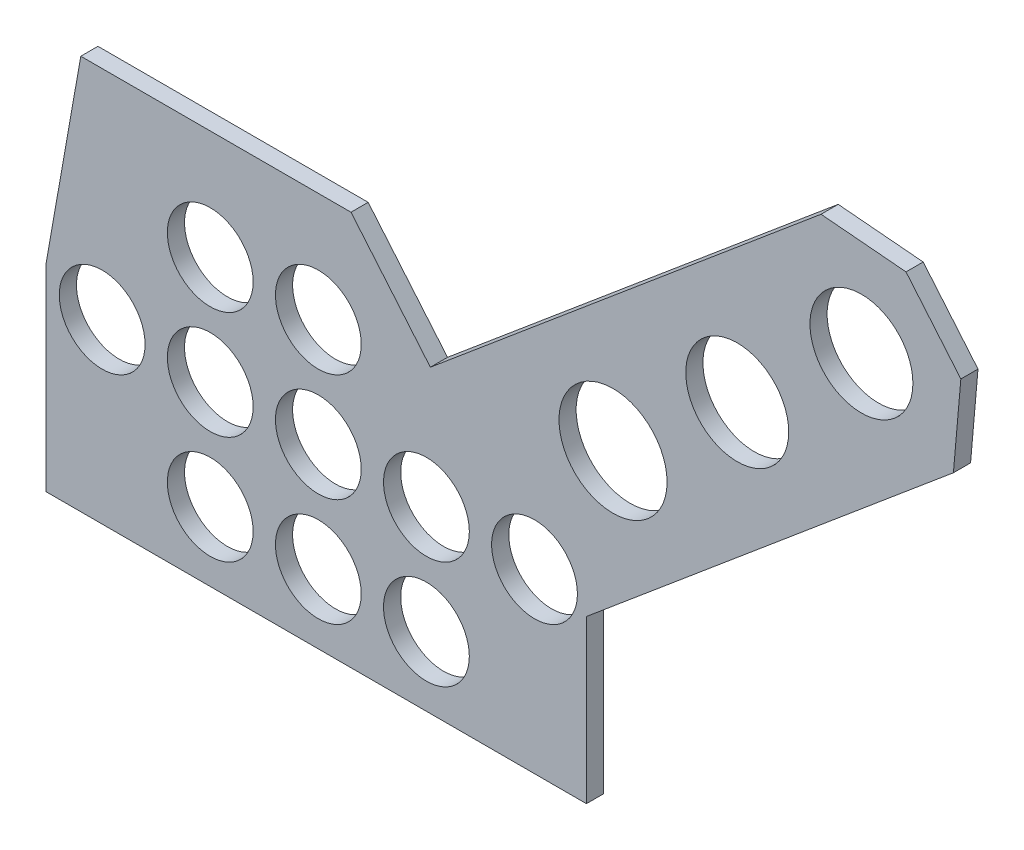
SolidWorks part; units mm, degrees
ref_plane "Front Plane" through (0, 0, 0) normal (0, 0, 1) x (1, 0, 0)
ref_plane "Top Plane" through (0, 0, 0) normal (0, 1, 0) x (1, 0, 0)
ref_plane "Right Plane" through (0, 0, 0) normal (1, 0, 0) x (0, 0, -1)
sketch "Sketch2" plane through (0, 0, 0) normal (0, 0, 1) x (1, 0, 0)
  line L23 (0, 0) -> (100, 0)
  line L24 (100, 0) -> (100, 30)
  line L25 (100, 30) -> (167.9013, 86.976)
  line L26 (167.9013, 86.976) -> (169.2768, 102.6974)
  line L27 (169.2768, 102.6974) -> (159.1326, 114.7868)
  line L28 (159.1326, 114.7868) -> (143.4111, 116.1622)
  line L31 (56.4359, 73) -> (6.4359, 73)
  line L32 (6.4359, 73) -> (0, 36.5)
  line L33 (0, 36.5) -> (0, 0)
  line L34 (164.2047, 108.7421) -> (100, 54.868) construction
  line L35 (56.4359, 73) -> (71.1187, 55.5017)
  line L36 (71.1187, 55.5017) -> (143.4111, 116.1622)
  line L37 (143.4111, 116.1622) -> (167.9013, 86.976) construction
  point P2 (0, 0)
  point P15 (0, 0)
  point P16 (5.4947, 73)
  point P17 (0, 0)
  dimension "D1" = 130
  dimension "D2" = 50
  dimension "D3" = 73
  dimension "D4" = 30
  dimension "D5" = 101.6
  dimension "D6" = 100
  dimension "D7" = 38.1
  dimension "D8" = 170
  dimension "D9" = 36.5
extrude "Base Extrude" add sketch "Sketch2" along normal blind 3.175 contours L31 L32 L33 L23 L24 L25 L26 L27 L28 L36 L35
sketch "Sketch3" plane through (0, 0, 3.175) normal (0, 0, 1) x (1, 0, 0)
  line L0 (164.2047, 108.7421) -> (94.2774, 50.0662) construction
  line L1 (169.2768, 102.6974) -> (159.1326, 114.7868) construction
  circle A0 centre (150.8824, 97.5634) radius 9.525
  circle A1 centre (127.9011, 78.2798) radius 9.525
  circle A2 centre (104.9197, 58.9961) radius 10
  circle A3 centre (30.3915, 52.7667) radius 7.9375
  circle A4 centre (50.3915, 52.7667) radius 7.9375
  circle A5 centre (10.3915, 32.7667) radius 7.9375
  circle A6 centre (30.3915, 32.7667) radius 7.9375
  circle A7 centre (50.3915, 32.7667) radius 7.9375
  circle A8 centre (70.3915, 32.7667) radius 7.9375
  circle A9 centre (30.3915, 12.7667) radius 7.9375
  circle A10 centre (50.3915, 12.7667) radius 7.9375
  circle A11 centre (70.3915, 12.7667) radius 7.9375
  circle A12 centre (90.3915, 32.7667) radius 7.9375
  point P24 (0, 0)
  point P25 (104.9246, 59.0002)
  point P30 (0, 0)
  point P31 (0, 0)
  dimension "D1" = 15.875
  dimension "D2" = 20
  dimension "D11" = 19.05
  dimension "D3" = 30
  dimension "D4" = 20
  dimension "D5" = 20
  dimension "D6" = 20
  dimension "D7" = 20
  dimension "D8" = 20
  dimension "D9" = 20
  dimension "D10" = 30
extrude "Holes" cut sketch "Sketch3" against normal through all
